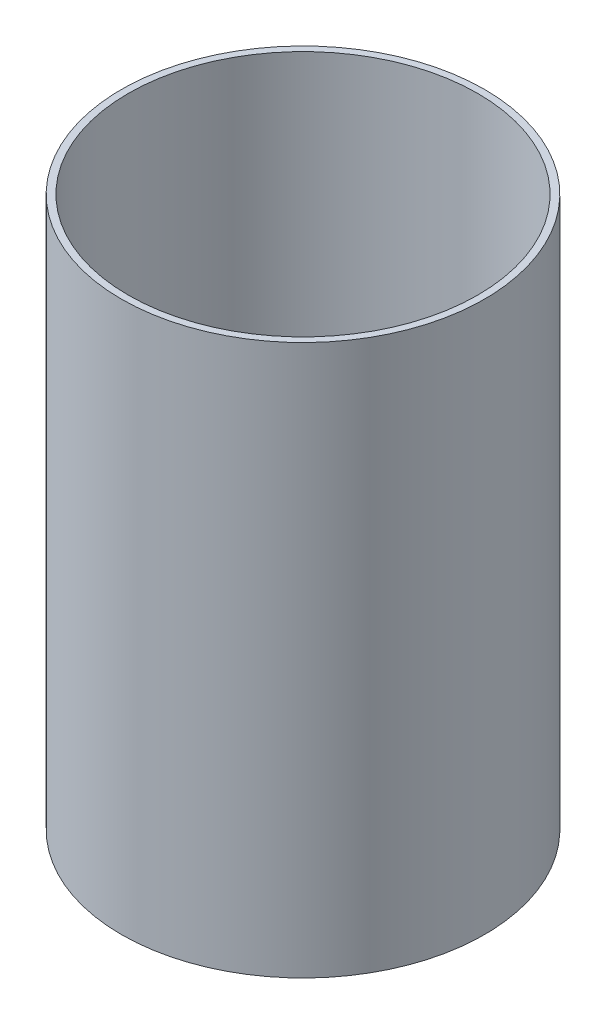
SolidWorks part; units mm, degrees
ref_plane "Front Plane" through (0, 0, 0) normal (0, 0, 1) x (1, 0, 0)
ref_plane "Top Plane" through (0, 0, 0) normal (0, 1, 0) x (1, 0, 0)
ref_plane "Right Plane" through (0, 0, 0) normal (1, 0, 0) x (0, 0, -1)
sketch "Sketch1" plane through (0, 0, 0) normal (0, 1, 0) x (1, 0, 0)
  circle A0 centre (0, 0) radius 39.6
  circle A1 centre (0, 0) radius 38.1
  dimension "D1" = 79.2
  dimension "D2" = 76.2
extrude "Boss-Extrude1" add sketch "Sketch1" along normal blind 120
